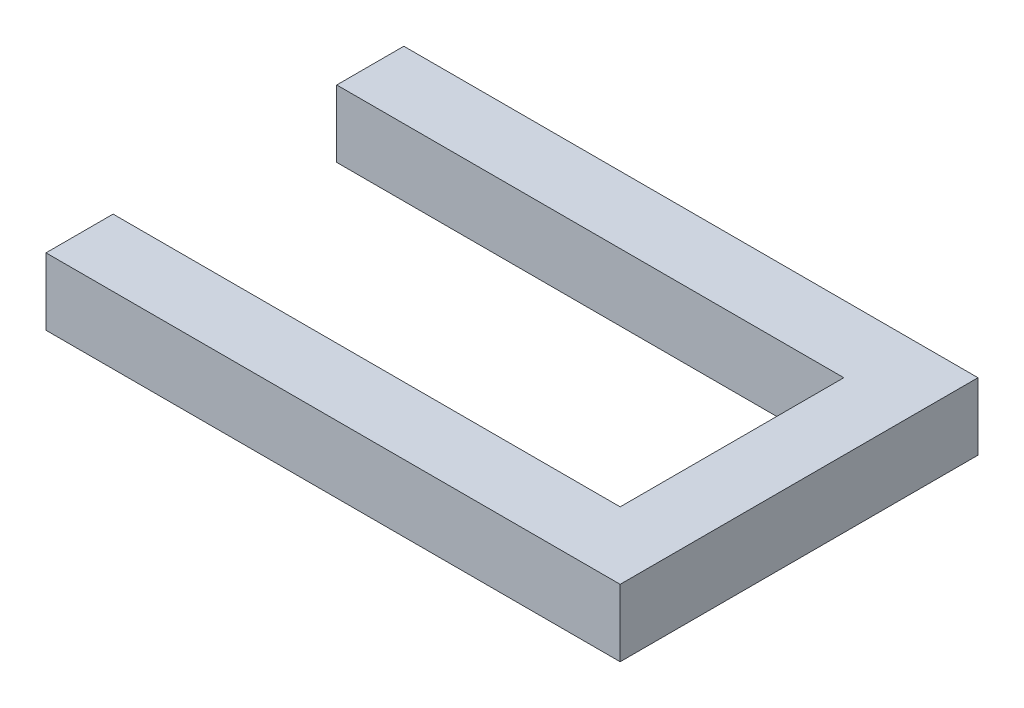
SolidWorks part; units mm, degrees
ref_plane "Front Plane" through (0, 0, 0) normal (0, 0, 1) x (1, 0, 0)
ref_plane "Top Plane" through (0, 0, 0) normal (0, 1, 0) x (1, 0, 0)
ref_plane "Right Plane" through (0, 0, 0) normal (1, 0, 0) x (0, 0, -1)
sketch "Sketch1" plane through (0, 0, 0) normal (0, 0, 1) x (1, 0, 0)
  line L1 (-88.9, 6.35) -> (-127, 6.35)
  line L2 (-88.9, 6.35) -> (-88.9, -31.75)
  line L3 (-88.9, -31.75) -> (-127, -31.75)
  line L4 (-127, 6.35) -> (-127, -31.75)
  line L5 (-88.9, 6.35) -> (-88.9, 0) construction
  line L6 (-26.4, 6.35) -> (-87.9, 6.35) construction
  dimension "D1" = 38.1
  dimension "D2" = 38.1
extrude "Boss-Extrude1" add sketch "Sketch1" along normal blind 101.6 and the other way blind 101.6
sketch "Sketch2" plane through (-127, 0, 0) normal (-1, 0, 0) x (0, 0, 1)
  line L0 (-101.6, -31.75) -> (101.6, -31.75) construction
  line L1 (101.6, 6.35) -> (63.5, 6.35)
  line L2 (101.6, 6.35) -> (101.6, -31.75)
  line L3 (101.6, -31.75) -> (63.5, -31.75)
  line L4 (63.5, 6.35) -> (63.5, -31.75)
  line L6 (-101.6, 6.35) -> (-63.5, 6.35)
  line L7 (-101.6, 6.35) -> (-101.6, -31.75)
  line L8 (-101.6, -31.75) -> (-63.5, -31.75)
  line L9 (-63.5, 6.35) -> (-63.5, -31.75)
  dimension "D1" = 38.1
  dimension "D2" = 38.1
extrude "Boss-Extrude2" add sketch "Sketch2" along normal up to surface (287.9441 mm away)
